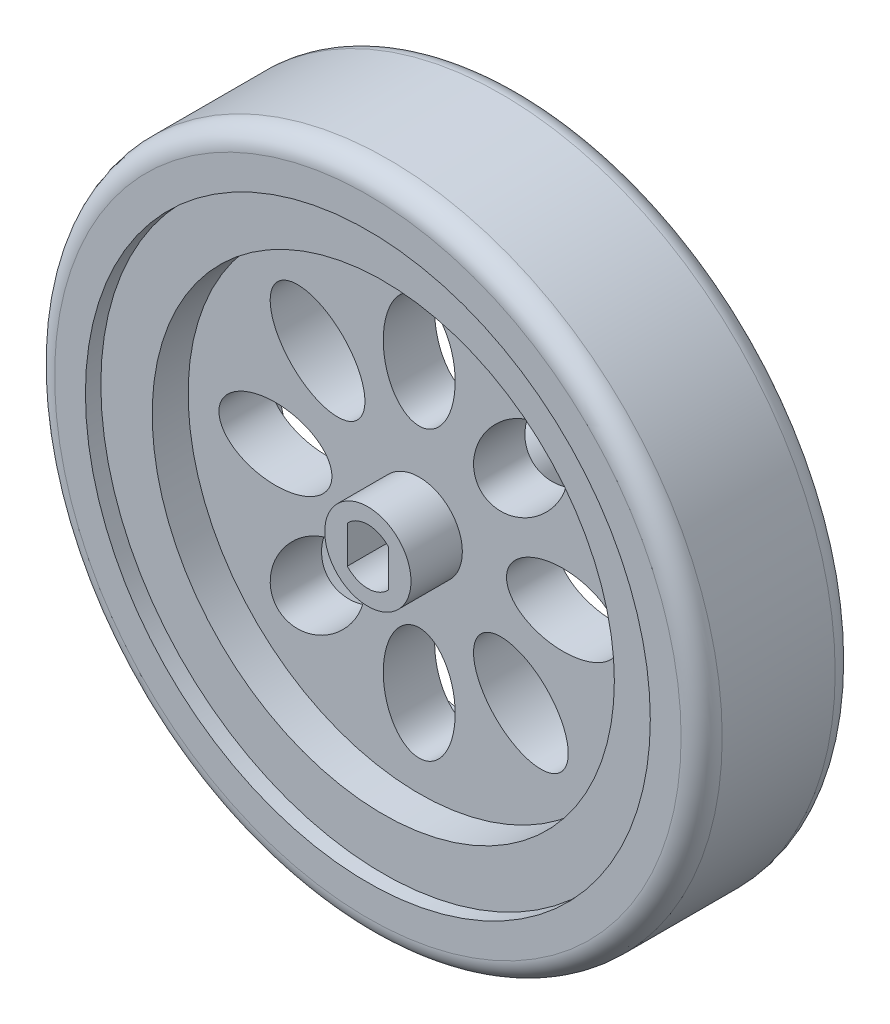
SolidWorks part; units mm, degrees
ref_plane "Front Plane" through (0, 0, 0) normal (0, 0, 1) x (1, 0, 0)
ref_plane "Top Plane" through (0, 0, 0) normal (0, 1, 0) x (1, 0, 0)
ref_plane "Right Plane" through (0, 0, 0) normal (1, 0, 0) x (0, 0, -1)
sketch "Sketch1" plane through (0, 0, 0) normal (0, 0, 1) x (1, 0, 0)
  circle A0 centre (0, 0) radius 32.5
  circle A1 centre (0, 0) radius 27.5
  dimension "D1" = 65
  dimension "D2" = 55
extrude "Boss-Extrude1" add sketch "Sketch1" along normal mid plane 15
fillet "Fillet1" radius 2 2 edges at (32.5, 0, -7.5) (32.5, 0, 7.5)
sketch "Sketch3" plane through (0, 0, 7.5) normal (0, 0, 1) x (1, 0, 0)
  line L0 (-2, 1.8138) -> (-2, -1.8138)
  line L1 (2, 1.8138) -> (2, -1.8138)
  circle A0 centre (0, 0) radius 4.2
  arc A1 (-2, -1.8138) -> (2, -1.8138) centre (0, 0) ccw
  arc A2 (2, 1.8138) -> (-2, 1.8138) centre (0, 0) ccw
  dimension "D1" = 5.4
  dimension "D4" = 8.4
  dimension "D2" = 2
  dimension "D3" = 2
extrude "Boss-Extrude2" add sketch "Sketch3" against normal offset from surface (18.85 mm away) 3.85 separate body up to face at (30.5, 0, -7.5) offset beyond the face yes
sketch "Sketch4" plane through (0, 0, 0) normal (0, 0, 1) x (1, 0, 0)
  circle A0 centre (0, 0) radius 27.5
  circle A1 centre (0, 0) radius 27.5 construction
  circle A2 centre (0, 0) radius 22.5
  dimension "D1" = 5
extrude "Boss-Extrude3" add sketch "Sketch4" along normal mid plane 12
sketch "Sketch5" plane through (0, 0, 0) normal (0, 0, 1) x (1, 0, 0)
  circle A0 centre (0, 0) radius 22.5
  circle A1 centre (0, 0) radius 4.2
  circle A2 centre (0, 0) radius 22.5 construction
  circle A3 centre (0, 0) radius 4.2 construction
extrude "Boss-Extrude4" add sketch "Sketch5" along normal mid plane 5
sketch "Sketch7" plane through (0, 0, 0) normal (0, 0, 1) x (1, 0, 0)
  ellipse E0 centre (0, 14) end of major axis (0, 19.5) minor radius 3.5
  dimension "D1" = 11
  dimension "D2" = 7
  dimension "D3" = 14
extrude "Cut-Extrude1" cut sketch "Sketch7" against normal through all both and the other way through all
pattern_circular "CirPattern1" count 8 over 360 about axis through (0, 0, 6) along (0, 0, -1) of "Cut-Extrude1" reverse direction yes
ref_plane "Plane1" through (32.5, 0, 0) normal (1, 0, 0) x (0, 0, -1)
ref_plane "Plane2" through (-32.5, 0, 0) normal (-1, 0, 0) x (0, 0, 1)
ref_plane "Plane3" through (0, 32.5, 0) normal (0, 1, 0) x (1, 0, 0)
ref_plane "Plane4" through (0, -32.5, 0) normal (0, -1, 0) x (-1, 0, 0)
